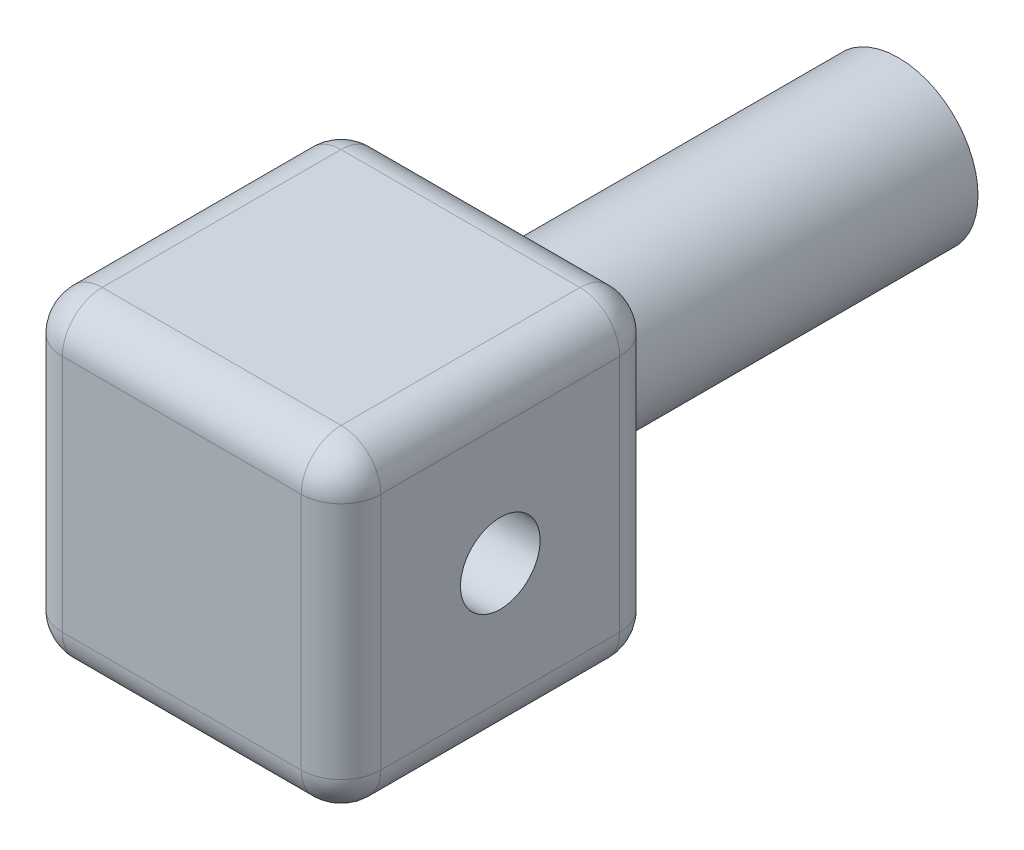
SolidWorks part; units mm, degrees
ref_plane "Front Plane" through (0, 0, 0) normal (0, 0, 1) x (1, 0, 0)
ref_plane "Top Plane" through (0, 0, 0) normal (0, 1, 0) x (1, 0, 0)
ref_plane "Right Plane" through (0, 0, 0) normal (1, 0, 0) x (0, 0, -1)
sketch "Box Sketch" plane through (0, 0, 0) normal (0, 0, 1) x (1, 0, 0)
  line L1 (-40, 40) -> (40, 40)
  line L2 (-40, 40) -> (-40, -40)
  line L3 (-40, -40) -> (40, -40)
  line L4 (40, 40) -> (40, -40)
  line L5 (-40, 40) -> (40, -40) construction
  line L6 (-40, -40) -> (40, 40) construction
  point P0 (0, 0)
  dimension "D1" = 80
extrude "Box Extrude" add sketch "Box Sketch" along normal blind 80
fillet "Box Fillet" radius 10 12 edges at (-40, -40, 40) (0, -40, 80) (40, -40, 40) (0, -40, 0) (40, 40, 40) (0, 40, 80) (-40, 40, 40) (0, 40, 0) (-40, 0, 80) (-40, 0, 0) (40, 0, 80) (40, 0, 0)
sketch "Pole Sketch" plane through (0, 0, 0) normal (0, 0, -1) x (-1, 0, 0)
  circle A0 centre (0, 0) radius 20
  dimension "D1" = 40
extrude "Pole Extrude" add sketch "Pole Sketch" along normal blind 100
sketch "Hole Sketch" plane through (-40, 0, 0) normal (-1, 0, 0) x (0, 0, 1)
  line L0 (0, 0) -> (80, 0) construction
  line L3 (80, 40) -> (80, -40) construction
  circle A0 centre (40, 0) radius 10
  point P4 (40, 0)
  dimension "D1" = 20
extrude "Hole Cut" cut sketch "Hole Sketch" against normal up to surface (80 mm away) up to face at (40, 0, 40)
